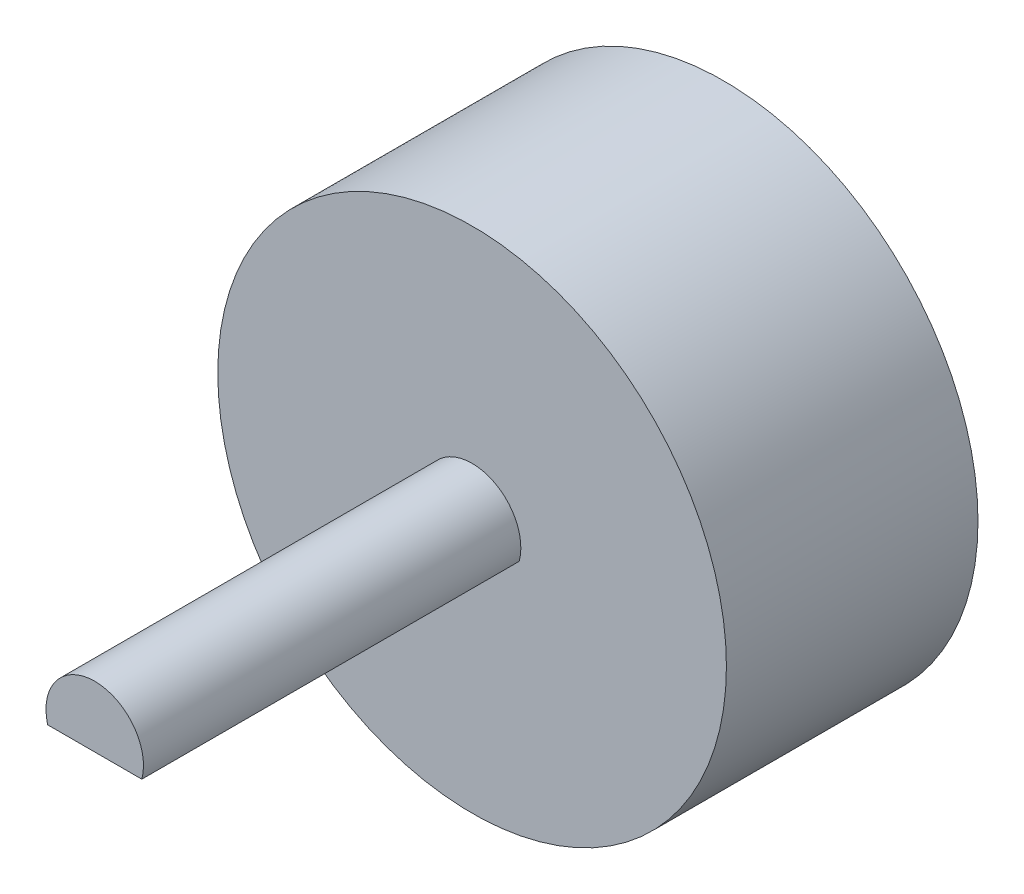
SolidWorks part; units mm, degrees
ref_plane "Front Plane" through (0, 0, 0) normal (0, 0, 1) x (1, 0, 0)
ref_plane "Top Plane" through (0, 0, 0) normal (0, 1, 0) x (1, 0, 0)
ref_plane "Right Plane" through (0, 0, 0) normal (1, 0, 0) x (0, 0, -1)
sketch "Sketch1" plane through (0, 0, 0) normal (0, 0, 1) x (1, 0, 0)
  line L0 (-2.995, -0.8) -> (2.995, -0.8)
  circle A0 centre (0, 0) radius 16.175
  arc A1 (-2.995, -0.8) -> (2.995, -0.8) centre (0, 0) cw
  dimension "D1" = 32.35
  dimension "D3" = 3.1
  dimension "D2" = 5.99
extrude "Boss-Extrude1" add sketch "Sketch1" along normal blind 16 contours A1 L0 | A0 L0 A1 region at (0, 0.8955, 0) region at (-15.7175, 0, 0)
extrude "Boss-Extrude2" add sketch "Sketch1<3>" along normal blind 24 from surface contours A1 L0 region at (0, 0.8955, 0) starting at face at (16.175, 0, 16)
sketch "Sketch1<3>" plane through (0, 0, 0) normal (0, 0, 1) x (1, 0, 0) same geometry as "Sketch1"
